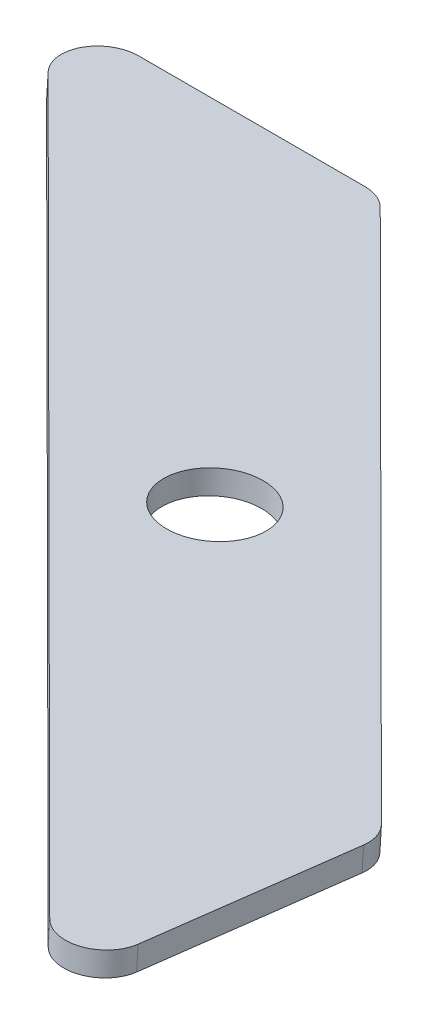
SolidWorks part; units mm, degrees
material "Plain Carbon Steel"
ref_plane "Front Plane" through (0, 0, 0) normal (0, 0, 1) x (1, 0, 0)
ref_plane "Top Plane" through (0, 0, 0) normal (0, 1, 0) x (1, 0, 0)
ref_plane "Right Plane" through (0, 0, 0) normal (1, 0, 0) x (0, 0, -1)
ref_axis "Axis1" through (200.0538, 113.7957, 921.4109) along (-0.061, 0.065, 0.996)
ref_axis "Axis2" through (-200.2636, 113.5719, 917.9832) along (0.061, 0.065, 0.996)
ref_plane "Plane1" through (0, 53.3914, -3.4869) normal (0, -0.9979, 0.0652) x (-1, 0, 0)
ref_plane "Plane2" through (0, 40.7184, -2.6593) normal (0, -0.9979, 0.0652) x (-1, 0, 0)
sketch "Sketch1" plane through (0, 40.7184, -2.6593) normal (0, -0.9979, 0.0652) x (-1, 0, 0)
  line L0 (-197.905, -962.0464) -> (-157.6841, -921.8255)
  line L1 (-200.0538, -926.8682) -> (-169.1645, -1432.5629) construction
  line L2 (-200.2933, -921.8255) -> (200.2933, -921.8255) construction
  line L3 (-157.6841, -921.8255) -> (-135.2335, -921.8255)
  line L4 (-135.2335, -921.8255) -> (-196.6126, -983.2046)
  line L5 (-196.6126, -983.2046) -> (-197.905, -962.0464)
  line L6 (-146.4588, -921.8255) -> (-197.2588, -972.6255) construction
  circle A0 centre (-171.8588, -947.2255) radius 3.2639
  dimension "D1" = 6.5278
  dimension "D2" = 45
  dimension "D3" = 15.875
  dimension "D4" = 25.4
extrude "Boss-Extrude1" add sketch "Sketch1" along normal blind 1.5875
fillet "Fillet1" radius 2.54 4 edges at (197.905, 102.6232, 957.3937) (157.6841, 100.002, 917.2583) (135.2335, 100.002, 917.2583) (196.6126, 104.0021, 978.5069)
